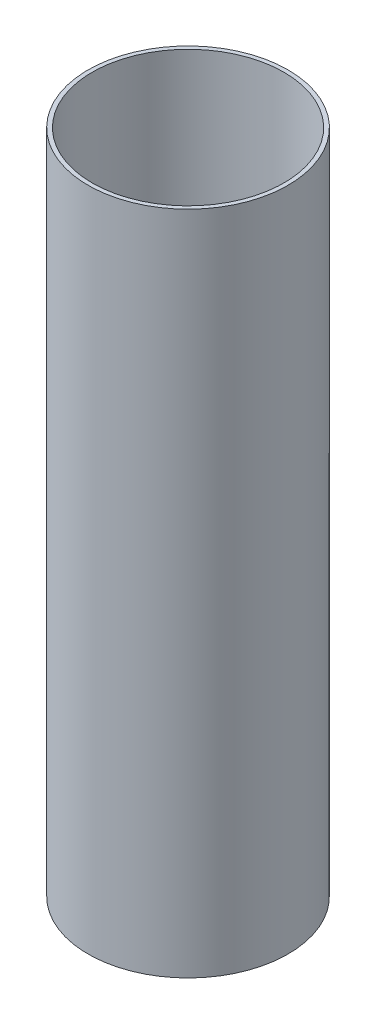
SolidWorks part; units mm, degrees
material "Hexcel AS4C (3000 Filaments)"
ref_plane "Front Plane" through (0, 0, 0) normal (0, 0, 1) x (1, 0, 0)
ref_plane "Top Plane" through (0, 0, 0) normal (0, 1, 0) x (1, 0, 0)
ref_plane "Right Plane" through (0, 0, 0) normal (1, 0, 0) x (0, 0, -1)
sketch "Sketch2" plane through (0, 0, 0) normal (0, 0, 1) x (1, 0, 0)
  line L0 (0, 0) -> (0, 51.225) construction
  line L1 (26.9875, 32.1729) -> (28.1305, 32.1729)
  line L2 (26.9875, 32.1729) -> (26.9875, -155.1521)
  line L3 (26.9875, -155.1521) -> (28.1305, -155.1521)
  line L4 (28.1305, 32.1729) -> (28.1305, -155.1521)
  point P5 (26.9875, 32.1729)
  point P8 (28.1305, -155.1521)
revolve "Revolve1" add sketch "Sketch2" angle 360 about L0
